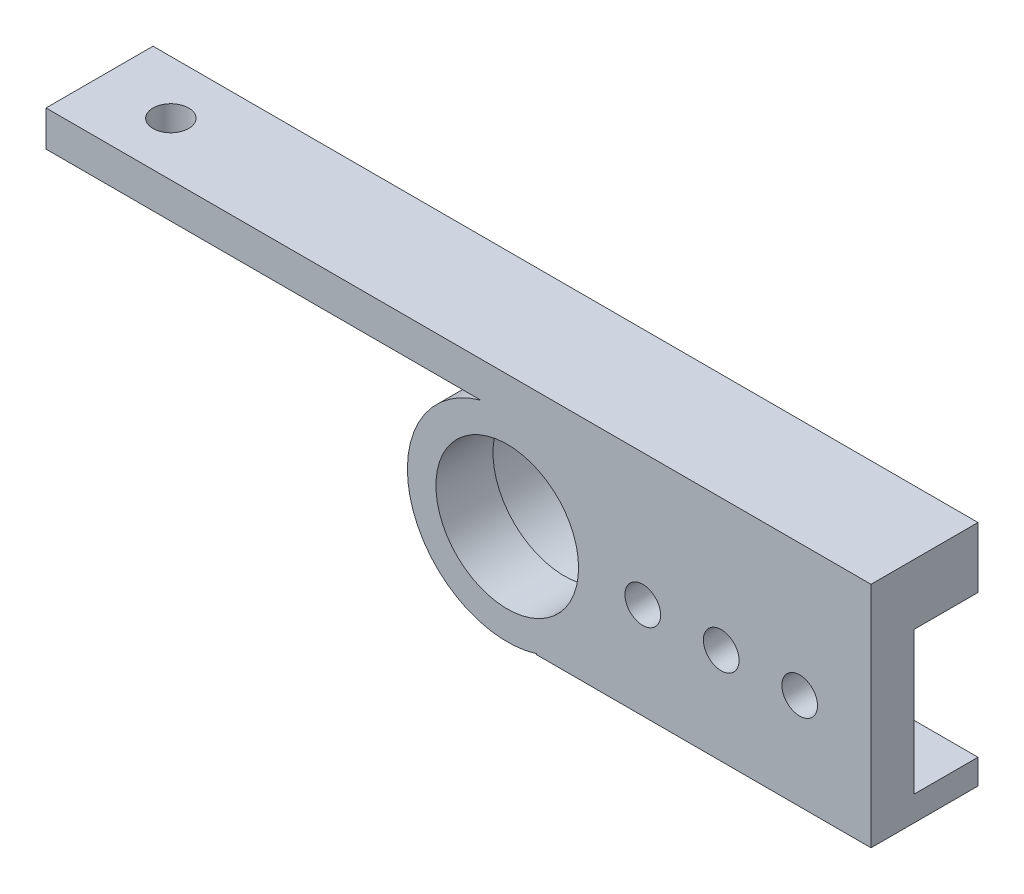
SolidWorks part; units mm, degrees
ref_plane "前视基准面" through (0, 0, 0) normal (0, 0, 1) x (1, 0, 0)
ref_plane "上视基准面" through (0, 0, 0) normal (0, 1, 0) x (1, 0, 0)
ref_plane "右视基准面" through (0, 0, 0) normal (1, 0, 0) x (0, 0, -1)
sketch "草图1" plane through (0, 0, 0) normal (0, 0, 1) x (1, 0, 0)
  line L1 (20, -10) -> (-20, -10)
  line L2 (20, -10) -> (20, 10)
  line L3 (20, 10) -> (-20, 10)
  line L4 (-20, -10) -> (-20, 10)
  line L5 (20, -10) -> (-20, 10) construction
  line L6 (20, 10) -> (-20, -10) construction
  point P0 (0, 0)
  dimension "D1" = 40
  dimension "D2" = 20
extrude "凸台-拉伸1" add sketch "草图1" along normal blind 6
sketch "草图2" plane through (0, 0, 6) normal (0, 0, 1) x (1, 0, 0)
  line L0 (20, -10) -> (20, 10) construction
  circle A0 centre (10, 0) radius 2.5
  circle A1 centre (-1, 0) radius 2.5
  circle A2 centre (-12, 0) radius 2.5
  dimension "D1" = 10
  dimension "D2" = 5
  dimension "D3" = 3
extrude "切除-拉伸1" cut sketch "草图2" against normal through all
sketch "草图3" plane through (0, 0, 6) normal (0, 0, 1) x (1, 0, 0)
  line L0 (20, 13.5) -> (20, 10)
  line L1 (20, -13.5) -> (-26.894, -13.5)
  line L3 (20, 13.5) -> (-26.894, 13.5)
  line L4 (-20, 10) -> (-20, -10)
  line L5 (-20, -10) -> (20, -10)
  line L6 (20, -10) -> (20, 10)
  line L7 (20, 10) -> (-20, 10)
  line L8 (-20, 10) -> (-20, -10)
  line L9 (-20, -10) -> (20, -10)
  line L10 (20, -10) -> (20, 10)
  line L11 (20, 10) -> (-20, 10)
  line L12 (-26.894, -13.5) -> (-26.894, 13.5)
  line L13 (20, -10.0394) -> (-26.894, 13.5) construction
  line L14 (20, 10.0394) -> (-26.894, -13.5) construction
  line L15 (20, -10) -> (20, -13.5)
  circle A0 centre (-31, 0) radius 11
  circle A1 centre (-31, 0) radius 14
  point P2 (0, 0)
  line M10 (-20, 10) -> (-20, -10)
  line M11 (-20, -10) -> (20, -10)
  line M13 (20, 10) -> (-20, 10)
  dimension "D3" = 22
  dimension "D4" = 28
  dimension "D2" = 3.5
  dimension "D1" = 0
extrude "凸台-拉伸2" add sketch "草图3" against normal blind 15 contours L3 A1 L1 L12 A0 | A1 L1 L15 M11 M10 | L1 A1 L8 A0 L12 | L8 A1 L3 L12 A0 | L8 A1 | A1 L0 L3 M10 M13 region at (-1.9449, 11.7771, 6) region at (-1.9449, -11.7771, 6) region at (-23.0173, 9.0328, 6) region at (-27.2274, 11.7946, 6) region at (-18.7882, 0, 6) region at (-23.0173, -9.0328, 6)
sketch "草图5" plane through (0, 0, 6) normal (0, 0, 1) x (1, 0, 0)
  circle A0 centre (-31, 0) radius 10
  circle A1 centre (-31, 0) radius 11 construction
  circle A2 centre (-31, 0) radius 11
  dimension "D1" = 20
extrude "凸台-拉伸3" add sketch "草图5" against normal blind 8
sketch "草图6" plane through (0, 0, 6) normal (0, 0, 1) x (1, 0, 0)
  circle A0 centre (-31, 0) radius 8.5
  circle A1 centre (-31, 0) radius 10 construction
  circle A2 centre (-31, 0) radius 10
  dimension "D1" = 17
sketch "草图7" plane through (0, 13.5, 0) normal (0, 1, 0) x (1, 0, 0)
  circle A0 centre (-16.8213, 3.0525) radius 3.3366
sketch "草图8" plane through (20, 0, 0) normal (1, 0, 0) x (0, 0, -1)
  line L1 (-6, 13.5) -> (9, 13.5)
  line L2 (-6, 13.5) -> (-6, 18.5)
  line L3 (-6, 18.5) -> (9, 18.5)
  line L4 (9, 13.5) -> (9, 18.5)
  dimension "D1" = 5
extrude "凸台-拉伸4" add sketch "草图8" against normal blind 200
sketch "草图9" plane through (0, 0, 6) normal (0, 0, 1) x (1, 0, 0)
  line L1 (-29.5663, 15.6648) -> (-25.1627, 15.6648)
  line L2 (-29.5663, 15.6648) -> (-29.5663, 11.9284)
  line L3 (-29.5663, 11.9284) -> (-25.1627, 11.9284)
  line L4 (-25.1627, 15.6648) -> (-25.1627, 11.9284)
extrude "凸台-拉伸5" add sketch "草图9" against normal through all
sketch "草图11" plane through (0, 18.5, 0) normal (0, 1, 0) x (1, 0, 0)
  line L0 (-95.6652, -6) -> (-95.6652, 9)
  line L1 (-180, -6) -> (20, -6) construction
  line L2 (-95.6652, 279.6057) -> (-95.6652, -90.3943) construction
  line L3 (-180, 9) -> (20, 9) construction
sketch "草图13" plane through (0, 18.5, 0) normal (0, 1, 0) x (1, 0, 0)
  line L1 (-95.6652, -6) -> (-183.1111, -6)
  line L2 (-95.6652, -6) -> (-95.6652, 12.5245)
  line L3 (-95.6652, 12.5245) -> (-183.1111, 12.5245)
  line L4 (-183.1111, -6) -> (-183.1111, 12.5245)
extrude "切除-拉伸2" cut sketch "草图13" against normal through all
sketch "草图14" plane through (0, 18.5, 0) normal (0, 1, 0) x (1, 0, 0)
  line L0 (-95.6652, 1.5) -> (-85.6652, 1.5) construction
  line L1 (-95.6652, -6) -> (-95.6652, 9) construction
  circle A0 centre (-85.6652, 1.5) radius 2.5
  dimension "D2" = 5
  dimension "D1" = 10
extrude "切除-拉伸3" cut sketch "草图14" against normal blind 10
